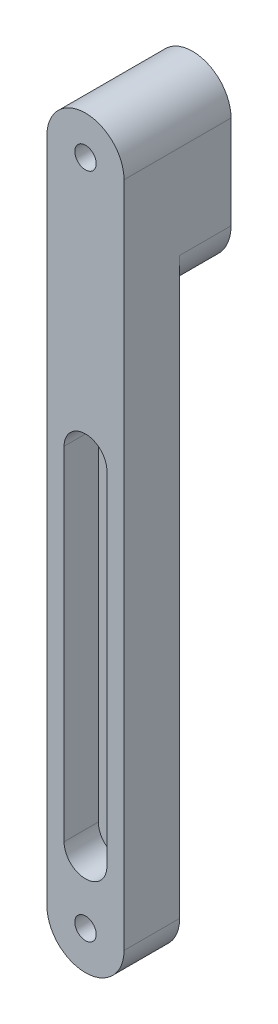
SolidWorks part; units mm, degrees
ref_plane "Front Plane" through (0, 0, 0) normal (0, 0, 1) x (1, 0, 0)
ref_plane "Top Plane" through (0, 0, 0) normal (0, 1, 0) x (1, 0, 0)
ref_plane "Right Plane" through (0, 0, 0) normal (1, 0, 0) x (0, 0, -1)
sketch "Sketch1" plane through (0, 0, 0) normal (0, 0, 1) x (1, 0, 0)
  line L0 (-9, 56.3943) -> (-9, -99.5197)
  line L1 (9, -99.5197) -> (9, 56.3943)
  circle A0 centre (0, 56.3943) radius 2.5
  circle A1 centre (0, -99.5197) radius 2.5
  arc A2 (9, 56.3943) -> (-9, 56.3943) centre (0, 56.3943) ccw
  arc A3 (-9, -99.5197) -> (9, -99.5197) centre (0, -99.5197) ccw
  dimension "D1" = 5
  dimension "D2" = 5
  dimension "D3" = 18
  dimension "D4" = 18
  dimension "D5" = 155.914
extrude "Extrude1" add sketch "Sketch1" along normal blind 13
sketch "Sketch2" plane through (0, 0, 13) normal (0, 0, 1) x (1, 0, 0)
  line L0 (-5, -4.5197) -> (-5, -84.5197)
  line L1 (5, -84.5197) -> (5, -4.5197)
  arc A0 (5, -4.5197) -> (-5, -4.5197) centre (0, -4.5197) ccw
  arc A1 (-5, -84.5197) -> (5, -84.5197) centre (0, -84.5197) ccw
  circle A2 centre (0, -99.5197) radius 2.5 construction
  dimension "D3" = 10
  dimension "D4" = 10
  dimension "D1" = 15
  dimension "D2" = 80
extrude "Extrude2" cut sketch "Sketch2" against normal blind 8
sketch "Sketch3" plane through (0, 0, 0) normal (0, 0, -1) x (-1, 0, 0)
  line L0 (-9, 56.3943) -> (-9, 24.5856)
  line L1 (-9, -99.5197) -> (-9, 56.3943) construction
  line L2 (-9, 24.5856) -> (9, 24.5856)
  line L3 (9, 56.3943) -> (9, -99.5197) construction
  line L4 (9, 24.5856) -> (9, 56.3943)
  arc A0 (9, 56.3943) -> (-9, 56.3943) centre (0, 56.3943) ccw
extrude "Extrude3" add sketch "Sketch3" along normal blind 12
fillet "Fillet1" radius 10 1 edges
fillet "Fillet2" radius 10 1 edges
sketch "Sketch4" plane through (0, 0, 13) normal (0, 0, 1) x (1, 0, 0)
  circle A0 centre (0, 56.3943) radius 2.5
extrude "Extrude4" cut sketch "Sketch4" against normal through all
